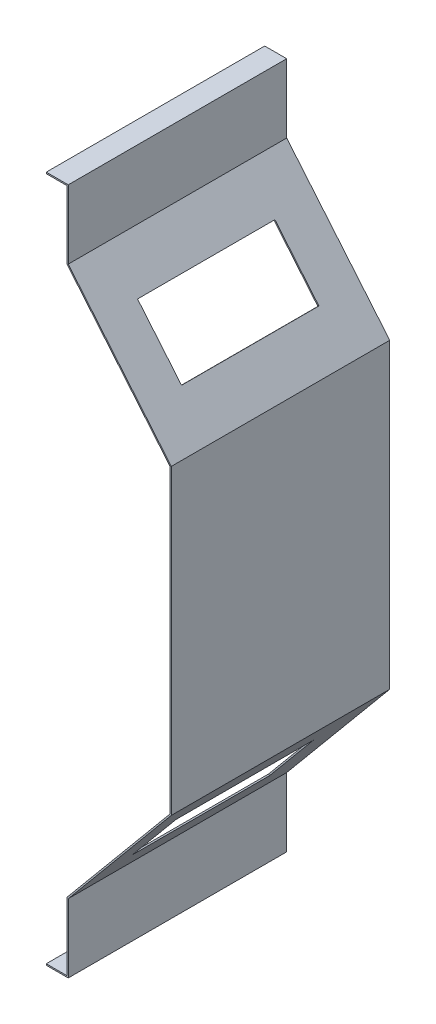
SolidWorks part; units mm, degrees
material "1023 Carbon Steel Sheet (SS)"
ref_plane "Front Plane" through (0, 0, 0) normal (0, 0, 1) x (1, 0, 0)
ref_plane "Top Plane" through (0, 0, 0) normal (0, 1, 0) x (1, 0, 0)
ref_plane "Right Plane" through (0, 0, 0) normal (1, 0, 0) x (0, 0, -1)
sketch "Sketch1" plane through (0, 0, 0) normal (0, 0, 1) x (1, 0, 0)
  line L0 (0, 110) -> (0, -110)
  line L1 (-75, 249) -> (-75, 200)
  line L2 (-75, 200) -> (0, 110)
  line L3 (0, 0) -> (60.5873, 0) construction
  line L4 (0, 0) -> (-93.7086, 0) construction
  line L5 (-75, -200) -> (0, -110)
  line L6 (-75, -249) -> (-75, -200)
  line L7 (-76, 249) -> (-76, 199.638)
  line L8 (-76, 199.638) -> (-1, 109.638)
  line L9 (-1, 109.638) -> (-1, -109.638)
  line L10 (-76, -199.638) -> (-1, -109.638)
  line L11 (-76, -249) -> (-76, -199.638)
  line L14 (-76, 249) -> (-91, 249)
  line L15 (-91, 250) -> (-75, 250)
  line L16 (-75, 249) -> (-75, 250)
  line L17 (-91, 250) -> (-91, 249)
  line L18 (-91, -250) -> (-91, -249)
  line L19 (-76, -249) -> (-91, -249)
  line L20 (-91, -250) -> (-75, -250)
  line L21 (-75, -250) -> (-75, -249)
  point P4 (0, 0)
  dimension "D1" = 220
  dimension "D2" = 250
  dimension "D3" = 90
  dimension "D4" = 75
  dimension "D6" = 15
  dimension "D7" = 1
  dimension "D8" = 250
  dimension "D9" = 117.1537
  dimension "D10" = 50
  dimension "D11" = 16
  dimension "D5" = 1
extrude "Boss-Extrude1" add sketch "Sketch1" along normal blind 159
sketch "Sketch2" plane through (54.0984, -45.082, 0) normal (0.7682, -0.6402, 0) x (0, 0, -1)
  line L0 (-159, -84.5043) -> (0, -84.5043) construction
  line L1 (-134, -118.0043) -> (-34, -118.0043)
  line L2 (-134, -118.0043) -> (-134, -168.0043)
  line L3 (-134, -168.0043) -> (-34, -168.0043)
  line L4 (-34, -118.0043) -> (-34, -168.0043)
  line L5 (-134, -118.0043) -> (-34, -168.0043) construction
  line L6 (-134, -168.0043) -> (-34, -118.0043) construction
  line L8 (-159, -201.6581) -> (-159, -84.5043) construction
  line L9 (-159, -201.6581) -> (0, -201.6581) construction
  point P0 (-84, -143.0043)
  dimension "D1" = 58.5
  dimension "D2" = 75
  dimension "D3" = 50
  dimension "D4" = 100
  dimension "D5" = 58.6537
extrude "Cut-Extrude1" cut sketch "Sketch2" against normal blind 160
sketch "Sketch5" plane through (54.0984, 45.082, 0) normal (0.7682, 0.6402, 0) x (0, 0, -1)
  line L1 (-130, 168.1581) -> (-30, 168.1581)
  line L2 (-130, 168.1581) -> (-130, 118.1581)
  line L3 (-130, 118.1581) -> (-30, 118.1581)
  line L4 (-30, 168.1581) -> (-30, 118.1581)
  line L5 (-130, 168.1581) -> (-30, 118.1581) construction
  line L6 (-130, 118.1581) -> (-30, 168.1581) construction
  line L7 (0, 84.5043) -> (0, 201.6581) construction
  line L8 (-159, 201.6581) -> (0, 201.6581) construction
  point P0 (-80, 143.1581)
  dimension "D1" = 80
  dimension "D2" = 50
  dimension "D3" = 100
  dimension "D4" = 58.5
extrude "Cut-Extrude2" cut sketch "Sketch5" against normal blind 160
sketch "Sketch6" plane through (54.0984, 45.082, 0) normal (0.7682, 0.6402, 0) x (0, 0, -1)
  circle A0 centre (-113.6352, 187.9347) radius 1.73
  dimension "D1" = 3.46
